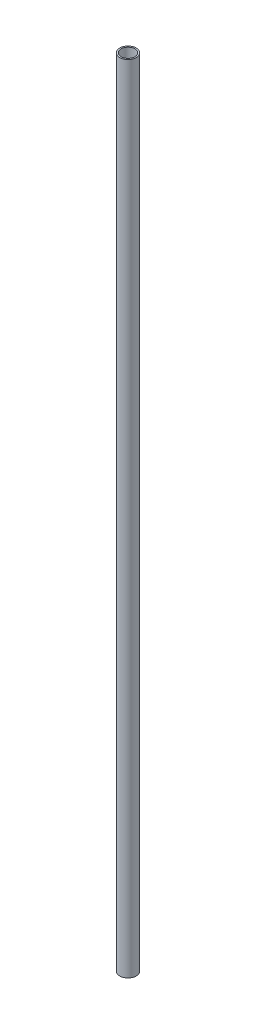
SolidWorks part; units mm, degrees
material "3003-H12"
ref_plane "Front Plane" through (0, 0, 0) normal (0, 0, 1) x (1, 0, 0)
ref_plane "Top Plane" through (0, 0, 0) normal (0, 1, 0) x (1, 0, 0)
ref_plane "Right Plane" through (0, 0, 0) normal (1, 0, 0) x (0, 0, -1)
sketch "Sketch1" plane through (0, 0, 0) normal (0, 1, 0) x (1, 0, 0)
  circle A0 centre (0, 0) radius 19.05
  circle A1 centre (0, 0) radius 15.78
  dimension "D1" = 38.1
  dimension "D2" = 3.27
extrude "Boss-Extrude1" add sketch "Sketch1" along normal blind 1823
ref_plane "topflap" through (0, 1373, 0) normal (0, 1, 0) x (1, 0, 0)
ref_plane "bottomflap" through (0, 883, 0) normal (0, 1, 0) x (1, 0, 0)
ref_plane "counterweight" through (0, 1193, 0) normal (0, 1, 0) x (1, 0, 0)
ref_plane "thread end" through (0, 10, 0) normal (0, -1, 0) x (-1, 0, 0)
thread "Thread1" pitch 2.1167 method cut profile "Thread Profile2" start angle 0, offset 0, length 0, pitch 2.1167, diameter 31.56
ref_plane "Plane2" through (15.78, 0, 0) normal (0, 0, 1) x (1, 0, 0)
sketch "Thread Profile2" plane through (15.78, 0, 0) normal (0, 0, 1) x (1, 0, 0)
  line L0 (0, 0) -> (0, 2.1167) construction
  line L1 (0, 0) -> (1.1457, 0.6615)
  line L2 (1.1457, 0.6615) -> (1.1457, 0.926)
  line L3 (1.1457, 0.926) -> (0, 1.5875)
  line L4 (1.1457, 0.7937) -> (0, 0.7937) construction
  line L11 (0, 0) -> (0, 1.5875)
  point P2 (0, 0)
  dimension "Pitch" = 2.1167
  dimension "Profile_Angle" = 60
  dimension "Profile_Land" = 0.2646
  dimension "Profile_Height" = 1.1457
equation "\"1.5n\"=37.2712"
